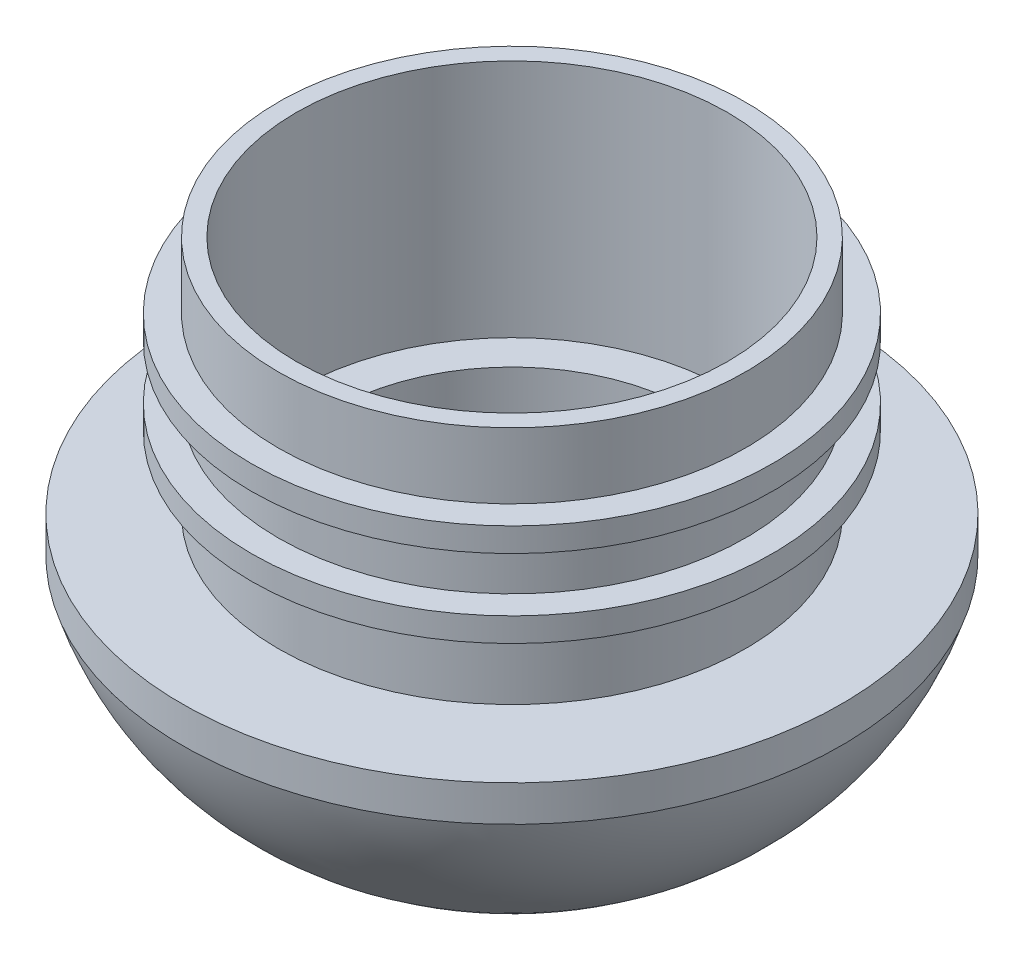
SolidWorks part; units mm, degrees
ref_plane "前基準面" through (0, 0, 0) normal (0, 0, 1) x (1, 0, 0)
ref_plane "上基準面" through (0, 0, 0) normal (0, 1, 0) x (1, 0, 0)
ref_plane "右基準面" through (0, 0, 0) normal (1, 0, 0) x (0, 0, -1)
sketch "草圖1" plane through (0, 0, 0) normal (0, 1, 0) x (1, 0, 0)
  circle A0 centre (0, 0) radius 19.5
  circle A1 centre (0, 0) radius 18
  dimension "D1" = 39
  dimension "D2" = 36
extrude "填料-伸長1" add sketch "草圖1" along normal blind 20
sketch "草圖3" plane through (0, 0, 0) normal (0, -1, 0) x (1, 0, 0)
  circle A0 centre (0, 0) radius 27.5
  dimension "D1" = 55
extrude "填料-伸長2" add sketch "草圖3" along normal blind 3
ref_plane "平面1" through (0, 8, 0) normal (0, 1, 0) x (1, 0, 0)
sketch "草圖4" plane through (0, 8, 0) normal (0, 1, 0) x (1, 0, 0)
  circle A0 centre (0, 0) radius 21.75
  dimension "D1" = 43.5
extrude "填料-伸長3" add sketch "草圖4" against normal blind 2
sketch "草圖6" plane through (0, 0, 0) normal (0, 1, 0) x (1, 0, 0)
  circle A0 centre (0, 0) radius 18
  dimension "D1" = 36
ref_plane "平面2" through (0, 11.5, 0) normal (0, 1, 0) x (1, 0, 0)
sketch "草圖8" plane through (0, 11.5, 0) normal (0, 1, 0) x (1, 0, 0)
  circle A0 centre (0, 0) radius 21.75
extrude "填料-伸長4" add sketch "草圖8" along normal blind 2 from offset 1
extrude "除料-伸長1" cut sketch "草圖6" along normal blind 35
ref_plane "平面3" through (0, -3, 0) normal (0, -1, 0) x (-1, 0, 0)
ref_plane "平面4" through (0, -18, 0) normal (0, -1, 0) x (-1, 0, 0)
sketch "草圖11" plane through (0, -18, 0) normal (0, -1, 0) x (-1, 0, 0)
  line L1 (0, 0) -> (0, 15) construction
  line L2 (0, 15) -> (0, -15) construction
  circle A0 centre (0, 0) radius 15
  dimension "D1" = 30
sketch "草圖18" plane through (0, 0, 0) normal (1, 0, 0) x (0, 0, -1)
  line L1 (-15, -18) -> (15, -18) construction
  line L3 (15, -18) -> (15, -3)
  line L5 (15, -3) -> (27.5, -3)
  line L6 (0, -18) -> (0, -3)
  line L7 (-30.25, -3) -> (30.25, -3) construction
  line L8 (0, -3) -> (0, -18)
  arc A1 (15, -18) -> (27.5, -3) centre (3.5694, 4.2338) ccw
revolve "旋轉3" add sketch "草圖18" angle 360 about L6 region at (0, -8.6546, -19.7528)
extrude "除料-伸長4" cut sketch "草圖11" against normal blind 18
ref_plane "平面5" through (0, -16, 0) normal (0, -1, 0) x (-1, 0, 0)
sketch "草圖20" plane through (0, -16, 0) normal (0, -1, 0) x (-1, 0, 0)
  circle A0 centre (0, 0) radius 14
  circle A1 centre (0, 0) radius 15
  dimension "D1" = 28
  dimension "D2" = 30
extrude "填料-伸長7" add sketch "草圖20" against normal blind 2
